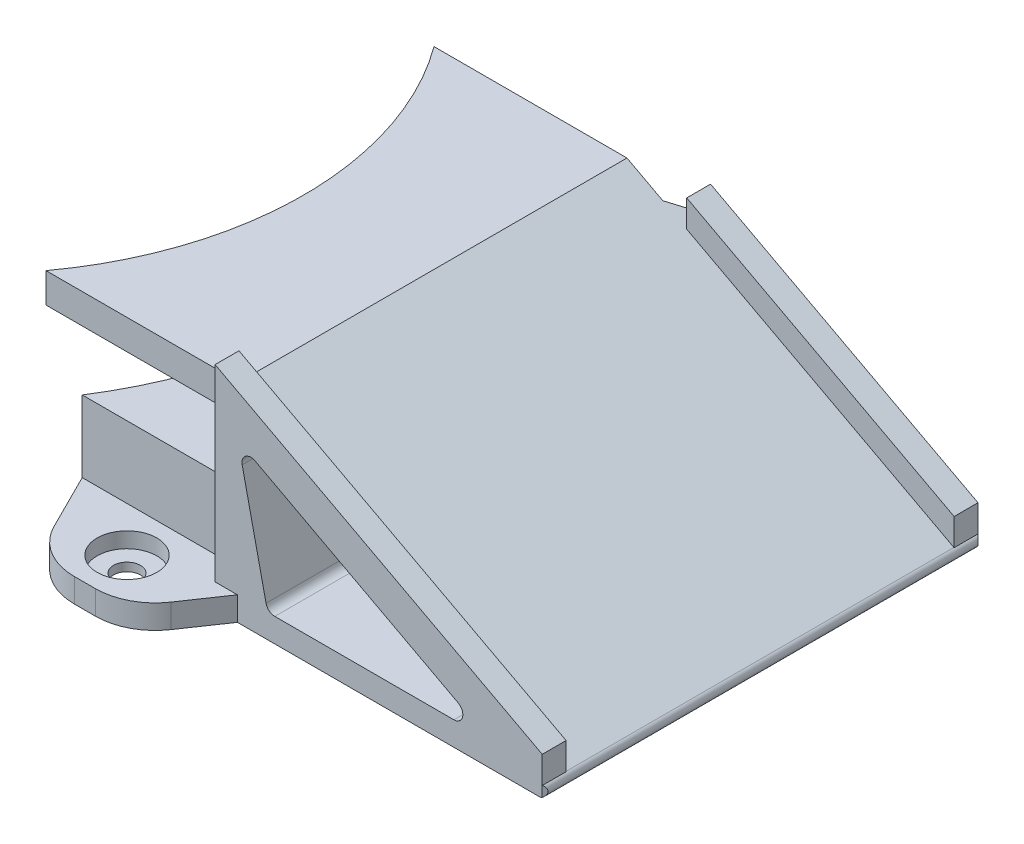
SolidWorks part; units mm, degrees
material "ABS"
ref_plane "Piano frontale" through (0, 0, 0) normal (0, 0, 1) x (1, 0, 0)
ref_plane "Piano superiore" through (0, 0, 0) normal (0, 1, 0) x (1, 0, 0)
ref_plane "Piano destro" through (0, 0, 0) normal (1, 0, 0) x (0, 0, -1)
sketch "Schizzo1" plane through (0, 0, 0) normal (0, 0, 1) x (1, 0, 0)
  line L0 (-115, 26) -> (0, 26)
  line L1 (0, 26) -> (0, 16)
  line L2 (0, 16) -> (-45, 16)
  line L3 (-45, 16) -> (-45, 0)
  line L4 (-45, 0) -> (58.3025, 0)
  line L5 (58.3025, 0) -> (0, 31)
  line L6 (0, 31) -> (-115, 31)
  line L7 (-115, 31) -> (-115, 26)
  line L8 (0, 26) -> (0, 31) construction
  dimension "D1" = 10
  dimension "D2" = 5
  dimension "D3" = 16
  dimension "D5" = 70
  dimension "D6" = 45
  dimension "D7" = 28
extrude "Estrusione-Estrusione1" add sketch "Schizzo1" along normal blind 90
sketch "Schizzo2" plane through (0, 31, 0) normal (0, 1, 0) x (1, 0, 0)
  line L0 (-15, -90) -> (-15, 0) construction
  line L1 (0, -90) -> (-115, -90) construction
  line L2 (0, 0) -> (-115, 0) construction
  line L3 (-32.3269, 0) -> (58.3025, 0) construction
  line L4 (0, -90) -> (0, 0) construction
  line L5 (-32.3269, -65) -> (58.3025, -65)
  line L6 (58.3025, -65) -> (58.3025, 0) construction
  line L7 (-32.3269, 0) -> (-115, 0)
  line L8 (-115, 0) -> (-115, -90)
  line L9 (-115, -90) -> (58.3025, -90)
  line L10 (58.3025, -90) -> (58.3025, -65)
  line L11 (58.3025, -32.5) -> (-76.6975, -32.5) construction
  arc A1 (-32.3269, -65) -> (-32.3269, 0) centre (-76.6975, -32.5) ccw
  dimension "D1" = 110
  dimension "D2" = 15
  dimension "D5" = 65
  dimension "D6" = 135
extrude "Taglio-Estrusione1" cut sketch "Schizzo2" against normal blind 60
sketch "Schizzo3" plane through (0, 0, 0) normal (0, -1, 0) x (1, 0, 0)
  line L0 (-76.6975, 32.5) -> (58.3025, 32.5) construction
  line L1 (58.3025, 65) -> (58.3025, 0) construction
  circle A0 centre (-76.6975, 32.5) radius 60
  dimension "D1" = 120
  dimension "D2" = 135
extrude "Taglio-Estrusione2" cut sketch "Schizzo3" against normal blind 21
sketch "Schizzo4" plane through (0, 0, 0) normal (0, -1, 0) x (1, 0, 0)
  line L0 (-26.2619, 65) -> (-18.7619, 80)
  line L1 (-18.7619, 80) -> (-3.7619, 80)
  line L3 (58.3025, 65) -> (-26.2619, 65) construction
  line L4 (-26.2619, 0) -> (-18.7619, -15)
  line L5 (-18.7619, -15) -> (-3.7619, -15)
  line L7 (-26.2619, 0) -> (58.3025, 0) construction
  line L8 (-11.2619, -15) -> (-11.2619, 80) construction
  line L9 (-26.2619, 0) -> (3.7381, 0)
  line L10 (3.7381, 65) -> (-26.2619, 65)
  line L11 (3.7381, 65) -> (3.7381, 69)
  line L12 (3.7381, 69) -> (-3.7619, 80)
  line L13 (3.7381, 0) -> (3.7381, -4)
  line L14 (3.7381, -4) -> (-3.7619, -15)
  point P16 (-11.2619, 0)
  point P17 (-3.7619, 81.3718)
  dimension "D1" = 15
  dimension "D2" = 15
  dimension "D3" = 30
  dimension "D4" = 4
  dimension "D5" = 4
extrude "Estrusione-Estrusione2" add sketch "Schizzo4" against normal blind 4
hole_wizard "Foro lamato per Vite M4 a testa cilindrica piana-1" positions "Schizzo3D1" profile "Schizzo5" counterbore size "M4" standard "ISO"
sketch3d "Schizzo3D1"
  line L0 (-11.2619, 4, 72.5) -> (-11.2619, 4, -7.5) construction
  line L2 (-26.2619, 4, 65) -> (3.7381, 4, 65) construction
  line L3 (3.7381, 4, 0) -> (-26.2619, 4, 0) construction
  point P0 (-11.2619, 4, 72.5)
  point P2 (-11.2619, 4, -7.5)
  point P10 (-11.2619, 4, 65)
  dimension "D1" = 7.5
  dimension "D2" = 7.5
sketch "Schizzo5" plane through (-11.2619, 4, 72.5) normal (1, 0, 0) x (0, 0, 1)
  line L0 (0, 0) -> (0, 9.3519)
  line L1 (0, 9.3519) -> (2.25, 8)
  line L2 (2.25, 8) -> (2.25, 2.6)
  line L3 (2.25, 2.6) -> (5, 2.6)
  line L4 (5, 2.6) -> (5, 0)
  line L5 (5, 0) -> (0, 0)
  line L10 (0, 9.3519) -> (-2.25, 8) construction
  line L11 (0, -6.35) -> (0, 107.95) construction
  dimension "Hole Dia." = 4.5
  dimension "Hole Depth" = 8
  dimension "C'Bore Dia." = 10
  dimension "C'Bore Depth" = 2.6
  dimension "Drill Angle" = 118
fillet "Raccordo3" radius 10 4 edges at (-18.7619, 2, -15) (-18.7619, 2, 80) (-3.7619, 2, -15) (-3.7619, 2, 80)
sketch "Schizzo9" plane through (0, 0, 65) normal (0, 0, 1) x (1, 0, 0)
  line L0 (3.7381, 0) -> (3.7381, 4)
  line L1 (3.7381, 4) -> (0, 4)
  line L2 (-26.2619, 4) -> (3.7381, 4) construction
  line L3 (0, 4) -> (0, 35.5303)
  line L4 (0, 35.5303) -> (54.8025, 6.3913)
  line L5 (54.8025, 6.3913) -> (54.8025, 0)
  line L6 (54.8025, 0) -> (3.7381, 0)
  line L7 (0, 16) -> (0, 26) construction
  line L8 (0, 31) -> (58.3025, 0) construction
  point P15 (0, 0)
  dimension "D1" = 4
  dimension "D2" = 3.5
extrude "Estrusione-Estrusione3" add sketch "Schizzo9" along normal blind 4
sketch "Schizzo10" plane through (0, 0, 0) normal (0, 0, -1) x (-1, 0, 0)
  line L0 (-54.8025, 0) -> (-54.8025, 6.3913)
  line L1 (-54.8025, 6.3913) -> (-10, 30.2132)
  line L2 (-10, 30.2132) -> (-10, 4)
  line L3 (-3.7381, 4) -> (26.2619, 4) construction
  line L4 (-10, 4) -> (-3.7381, 4)
  line L5 (-3.7381, 4) -> (-3.7381, 0)
  line L6 (-3.7381, 0) -> (-54.8025, 0)
  line L7 (0, 26) -> (0, 16) construction
  line L8 (-54.8025, 6.3913) -> (0, 35.5303) construction
  point P4 (-58.3025, 3.5944)
  point P15 (0, 0)
  point P16 (0, 0)
  point P18 (0, 0)
  point P21 (-2.5, 34.201)
  dimension "D1" = 10
extrude "Estrusione-Estrusione4" add sketch "Schizzo10" along normal blind 4
sketch "Schizzo6" plane through (0, 0, 69) normal (0, 0, 1) x (1, 0, 0)
  line L0 (6.7042, 24.9025) -> (40.7042, 6.8244)
  line L19 (40, 4) -> (10, 4)
  line L20 (8.5354, 5.1759) -> (4.5354, 23.2541)
  line L26 (54.8025, 6.3913) -> (0, 35.5303) construction
  line L27 (3.7381, 0) -> (54.8025, 0) construction
  line L28 (0, 35.5303) -> (0, 4) construction
  arc A0 (40, 4) -> (40.7042, 6.8244) centre (40, 5.5) ccw
  arc A1 (10, 4) -> (8.5354, 5.1759) centre (10, 5.5) cw
  arc A2 (6.7042, 24.9025) -> (4.5354, 23.2541) centre (6, 23.5781) ccw
  point P16 (8.7956, 4)
  point P19 (3.8329, 26.4293)
  dimension "D5" = 1.5
  dimension "D1" = 30
  dimension "D2" = 4
  dimension "D3" = 10
  dimension "D4" = 6
extrude "Taglio-Estrusione3" cut sketch "Schizzo6" against normal blind 179
chamfer "Smusso1" distance 4 angle 45 3 edges at (0, 28.5, 65) (0, 21, 0) (0, 10, 65)
fillet "Raccordo4" radius 1 1 edges at (58.3025, 0, 32.5)
chamfer "Smusso2" distance 4 angle 45 2 edges at (54.8025, 1, 0) (54.8025, 1, 65)
chamfer "Smusso3" distance 4 angle 45 1 edges at (10, 24.4165, 0)
